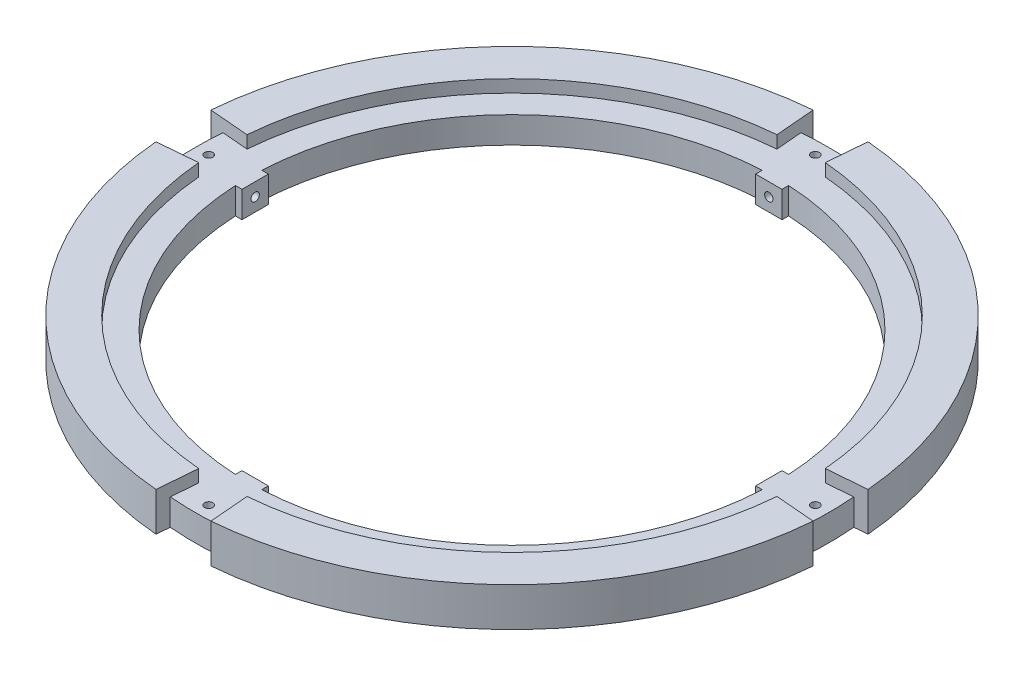
SolidWorks part; units mm, degrees
ref_plane "Front Plane" through (0, 0, 0) normal (0, 0, 1) x (1, 0, 0)
ref_plane "Top Plane" through (0, 0, 0) normal (0, 1, 0) x (1, 0, 0)
ref_plane "Right Plane" through (0, 0, 0) normal (1, 0, 0) x (0, 0, -1)
sketch "Sketch1" plane through (0, 0, 0) normal (0, 1, 0) x (1, 0, 0)
  circle A0 centre (0, 0) radius 139.7
  circle A1 centre (0, 0) radius 127
  circle A2 centre (0, 0) radius 152.4
extrude "Boss-Extrude1" add sketch "Sketch1" along normal blind 18.7 contours A2 A0 region at (-148.0895, 0, 0)
extrude "Boss-Extrude2" add sketch "Sketch1<3>" along normal blind 12.7 contours A0 A1 region at (-135.7487, 0, 0)
sketch "Sketch1<3>" plane through (0, 0, 0) normal (0, 1, 0) x (1, 0, 0) same geometry as "Sketch1"
sketch "Sketch2" plane through (0, 0, 0) normal (0, -1, 0) x (1, 0, 0)
  line L0 (0, -127) -> (0, -123.6662)
  line L1 (-6.35, -123.6662) -> (6.35, -123.6662)
  line L2 (6.35, -123.6662) -> (6.35, -125.2537)
  line L3 (6.35, -125.2537) -> (-6.35, -125.2537)
  line L4 (-6.35, -125.2537) -> (-6.35, -123.6662)
  line L5 (-6.35, -123.6662) -> (-6.35, -126.8412)
  line L6 (6.35, -123.6662) -> (6.35, -126.8412)
  line L7 (-123.6662, -6.35) -> (-126.8412, -6.35)
  line L8 (-123.6662, 6.35) -> (-126.8412, 6.35)
  line L9 (-123.6662, 6.35) -> (-123.6662, -6.35)
  line L10 (-6.35, 123.6662) -> (-6.35, 126.8412)
  line L11 (6.35, 123.6662) -> (6.35, 126.8412)
  line L12 (6.35, 123.6662) -> (-6.35, 123.6662)
  line L13 (123.6662, 6.35) -> (126.8412, 6.35)
  line L14 (123.6662, -6.35) -> (126.8412, -6.35)
  line L15 (123.6662, -6.35) -> (123.6662, 6.35)
  circle A0 centre (0, 0) radius 127 construction
  point P9 (0, -123.6662)
  point P28 (0, 0)
  circle M2 centre (0, 0) radius 127
  dimension "D1" = 1.5875
  dimension "D2" = 1.5875
  dimension "D4" = 12.7
  dimension "D3" = 4
extrude "Boss-Extrude3" add sketch "Sketch2" against normal blind 12.7 contours L9 L8 L7 M2 | L12 L11 L10 M2 | L15 L14 L13 M2 | L6 L3 L0 M2 | L3 L2 L1 L0 | L4 L3 L0 L1 | L3 L5 L0 M2 region at (-3.1254, 0, -126.101) region at (3.1254, 0, -126.101) region at (-3.175, 0, -124.4599) region at (3.175, 0, -124.4599) region at (-125.3069, 0, 0) region at (125.3069, 0, 0) region at (0, 0, 125.3069)
sketch "Sketch3" plane through (-123.6662, 0, 0) normal (1, 0, 0) x (0, 0, -1)
  line L0 (0, 12.7) -> (0, 0)
  line L1 (-6.35, 12.7) -> (6.35, 12.7) construction
  line L2 (-6.35, 0) -> (6.35, 0) construction
  circle A0 centre (0, 6.35) radius 2
extrude "Cut-Extrude1" cut sketch "Sketch3" against normal blind 25.4 contours L0 A0 | L0 A0 region at (-123.6662, 6.35, -0.8488) region at (-123.6662, 6.35, 0.8488)
pattern_circular "CirPattern1" count 4 every 90 about axis through (0, 12.7, 0) along (0, 1, 0) of "Cut-Extrude1"
sketch "Sketch4" plane through (0, 18.7, 0) normal (0, 1, 0) x (1, 0, 0)
  line L0 (-139.7, 0) -> (-152.4, 0)
  line L1 (-151.8699, -12.7) -> (0, 0)
  line L2 (0, 0) -> (-151.8708, 12.689)
  circle A0 centre (0, 0) radius 139.7 construction
  circle A1 centre (0, 0) radius 152.4 construction
  arc A2 (-151.8699, -12.7) -> (-151.8708, 12.689) centre (0, 0) cw
  circle A3 centre (0, 0) radius 139.7
  circle M4 centre (0, 0) radius 139.7
  circle M5 centre (0, 0) radius 152.4
  dimension "D1" = 152.4
  dimension "D2" = 12.7
  dimension "D3" = 12.7
extrude "Cut-Extrude4" cut sketch "Sketch4" against normal blind 6 contours L1 L0 M5 M4 | L2 L0 M4 M5 region at (-145.9725, 18.7, 6.0928) region at (-145.9728, 18.7, -6.0875)
sketch "Sketch5" plane through (0, 12.7, 0) normal (0, 1, 0) x (1, 0, 0)
  line L0 (-152.4, -0.0055) -> (-146.05, -0.0055)
  arc A0 (-151.8708, 12.689) -> (-151.8699, -12.7) centre (0, 0) ccw construction
  circle A1 centre (-146.05, -0.0055) radius 2
  dimension "D1" = 6.35
extrude "Cut-Extrude5" cut sketch "Sketch5" against normal blind 12.7 contours A1
pattern_circular "CirPattern2" count 4 every 90 about axis through (0, 18.7, 0) along (0, 1, 0) of "Cut-Extrude4", "Cut-Extrude5"
sketch "Sketch6" plane through (0, 18.7, 0) normal (0, 1, 0) x (1, 0, 0)
  line L0 (0, 0) -> (-151.8708, 12.689)
  line L1 (-151.8708, 12.689) -> (-158.1988, 13.2177)
  line L2 (0, 0) -> (-12.7, 151.8699)
  line L3 (-12.7, 151.8699) -> (-13.2292, 158.1978)
  arc A0 (-151.8708, 12.689) -> (-12.7, 151.8699) centre (0, 0) cw
  circle A2 centre (0, 0) radius 158.75
extrude "Boss-Extrude4" add sketch "Sketch6" against normal blind 18.7 contours L3 A2 L1 A0 region at (-154.8635, 18.7, -15.0039)
pattern_circular "CirPattern3" count 4 every 90 about axis through (0, 18.7, 0) along (0, 1, 0) of "Boss-Extrude4"
